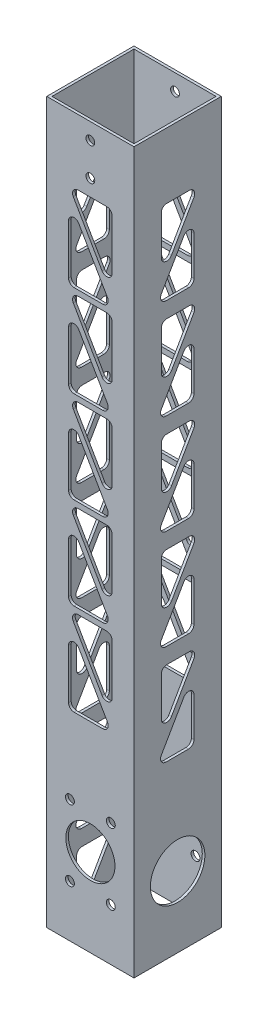
SolidWorks part; units mm, degrees
material "6061 Alloy"
ref_plane "Front Plane" through (0, 0, 0) normal (0, 0, 1) x (1, 0, 0)
ref_plane "Top Plane" through (0, 0, 0) normal (0, 1, 0) x (1, 0, 0)
ref_plane "Right Plane" through (0, 0, 0) normal (1, 0, 0) x (0, 0, -1)
sketch "Sketch1" plane through (0, 0, 0) normal (0, 1, 0) x (1, 0, 0)
  line L1 (25.4, 25.4) -> (-25.4, 25.4)
  line L2 (25.4, 25.4) -> (25.4, -25.4)
  line L3 (25.4, -25.4) -> (-25.4, -25.4)
  line L4 (-25.4, 25.4) -> (-25.4, -25.4)
  line L5 (25.4, 25.4) -> (-25.4, -25.4) construction
  line L6 (25.4, -25.4) -> (-25.4, 25.4) construction
  point P0 (0, 0)
  dimension "D1" = 50.8
extrude "Extrude-Thin1" add sketch "Sketch1" along normal blind 419.1 thin thin type one direction reverse wall 1.524
sketch "Sketch2" plane through (0, 0, 0) normal (0, 0, 1) x (1, 0, 0)
  line L0 (-36.2563, 68.2625) -> (38.5702, 68.2625) construction
  line L1 (-25.4, 0) -> (25.4, 0) construction
  line L2 (-25.4, 50.8) -> (25.4, 50.8) construction
  line L6 (25.4, 419.1) -> (25.4, 0) construction
  line L7 (-25.4, 419.1) -> (-25.4, 0) construction
  line L8 (-11.9062, 30.1778) -> (11.9063, 30.1778) construction
  line L9 (-11.9062, 71.4222) -> (11.9063, 71.4222) construction
  circle A0 centre (0, 50.8) radius 14.3002
  circle A1 centre (0, 50.8) radius 23.8125 construction
  circle A2 centre (-11.9062, 30.1778) radius 2.5908
  circle A3 centre (11.9063, 30.1778) radius 2.5908
  circle A4 centre (11.9063, 71.4222) radius 2.5908
  circle A5 centre (-11.9062, 71.4222) radius 2.5908
  point P11 (0, 50.8)
  dimension "D1" = 28.6004
  dimension "D3" = 17.4625
  dimension "D4" = 47.625
  dimension "D6" = 5.1816
  dimension "D2" = 50.8
  dimension "D5" = 60
extrude "Cut-Extrude1" cut sketch "Sketch2" along normal through all both and the other way through all
sketch "Sketch3" plane through (25.4, 0, 0) normal (1, 0, 0) x (0, 0, -1)
  line L0 (-25.4, 50.8) -> (25.4, 50.8) construction
  line L1 (-25.4, 65.1002) -> (-25.4, 36.4998) construction
  line L3 (25.4, 419.1) -> (25.4, 0) construction
  circle A0 centre (0, 41.275) radius 15.875
  point P9 (0, 50.8)
  dimension "D1" = 31.75
  dimension "D2" = 9.525
extrude "Cut-Extrude2" cut sketch "Sketch3" against normal up to surface (1.524 mm away) up to face at (23.876, 209.55, 0)
sketch "Sketch4" plane through (0, 0, 25.4) normal (0, 0, 1) x (1, 0, 0)
  line L0 (-25.4, 419.1) -> (25.4, 419.1) construction
  circle A0 centre (0, 409.575) radius 2.54
  circle A1 centre (0, 390.525) radius 2.54
  dimension "D1" = 5.08
  dimension "D2" = 9.525
  dimension "D3" = 28.575
hole_wizard "#10 Clearance Hole1" positions "Sketch5" profile "Sketch6" hole size "#10" standard "ANSI Inch" end condition through all
sketch "Sketch5" plane through (0, 0, 25.4) normal (0, 0, 1) x (1, 0, 0)
  point P0 (0, 390.525)
  point P3 (0, 409.575)
sketch "Sketch6" plane through (0, 390.525, 25.4) normal (1, 0, 0) x (0, -1, 0)
  line L0 (0, 0) -> (0, 50.8)
  line L1 (0, 50.8) -> (2.5527, 50.8)
  line L2 (2.5527, 50.8) -> (2.5527, 0)
  line L5 (2.5527, 0) -> (0, 0)
  line L11 (0, -6.35) -> (0, 107.95) construction
  dimension "Thru Hole Dia." = 5.1054
  dimension "Thru Hole Depth" = 50.8
sketch "Sketch7" plane through (0, 0, 25.4) normal (0, 0, 1) x (1, 0, 0)
  line L0 (-12.7, 419.1) -> (-12.7, 0) construction
  line L1 (12.7, 419.1) -> (12.7, 0) construction
  line L2 (-12.7, 0) -> (-25.4, 0) construction
  line L3 (-25.4, 0) -> (25.4, 0) construction
  line L4 (-25.4, 419.1) -> (-25.4, 0) construction
  line L5 (12.7, 0) -> (25.4, 0) construction
  line L6 (-25.4, 419.1) -> (25.4, 419.1) construction
  line L7 (-12.7, 381) -> (12.7, 381) construction
  line L8 (-12.7, 79.375) -> (12.7, 79.375) construction
  line L9 (-7.2007, 381) -> (9.525, 381)
  line L10 (12.7, 377.825) -> (12.7, 348.8552)
  line L11 (6.7754, 347.2677) -> (-9.9504, 376.2375)
  line L12 (-9.525, 330.6559) -> (7.2007, 330.6559)
  line L13 (-12.7, 333.8309) -> (-12.7, 362.8007)
  line L14 (-6.7754, 364.3882) -> (9.9504, 335.4184)
  line L15 (16.3954, 324.2553) -> (19.145, 325.8428) construction
  line L16 (-7.2007, 327.4809) -> (9.525, 327.4809)
  line L17 (12.7, 324.3059) -> (12.7, 295.3361)
  line L18 (6.7754, 293.7486) -> (-9.9504, 322.7184)
  line L19 (-12.7, 280.3118) -> (-12.7, 309.2816)
  line L20 (-9.525, 277.1368) -> (7.2007, 277.1368)
  line L21 (-6.7754, 310.8691) -> (9.9504, 281.8993)
  line L34 (-7.2007, 381) -> (-7.2007, 327.4809) construction
  line L35 (-7.2007, 273.9618) -> (9.525, 273.9618)
  line L36 (12.7, 270.7868) -> (12.7, 241.817)
  line L37 (6.7754, 240.2295) -> (-9.9504, 269.1993)
  line L38 (-12.7, 226.7927) -> (-12.7, 255.7626)
  line L39 (-9.525, 223.6177) -> (7.2007, 223.6177)
  line L40 (-6.7754, 257.3501) -> (9.9504, 228.3802)
  line L41 (-7.2007, 220.4427) -> (9.525, 220.4427)
  line L42 (12.7, 217.2677) -> (12.7, 188.2979)
  line L43 (6.7754, 186.7104) -> (-9.9504, 215.6802)
  line L44 (-12.7, 173.2736) -> (-12.7, 202.2435)
  line L45 (-9.525, 170.0986) -> (7.2007, 170.0986)
  line L46 (-6.7754, 203.831) -> (9.9504, 174.8611)
  line L47 (-7.2007, 166.9236) -> (9.525, 166.9236)
  line L48 (12.7, 163.7486) -> (12.7, 134.7788)
  line L49 (6.7754, 133.1913) -> (-9.9504, 162.1611)
  line L50 (-12.7, 119.7545) -> (-12.7, 148.7244)
  line L51 (-9.525, 116.5795) -> (7.2007, 116.5795)
  line L52 (-6.7754, 150.3119) -> (9.9504, 121.342)
  arc A0 (-9.9504, 376.2375) -> (-7.2007, 381) centre (-7.2007, 377.825) cw
  arc A1 (9.525, 381) -> (12.7, 377.825) centre (9.525, 377.825) cw
  arc A2 (12.7, 348.8552) -> (6.7754, 347.2677) centre (9.525, 348.8552) cw
  arc A3 (9.9504, 335.4184) -> (7.2007, 330.6559) centre (7.2007, 333.8309) cw
  arc A4 (-12.7, 362.8007) -> (-6.7754, 364.3882) centre (-9.525, 362.8007) cw
  arc A5 (-12.7, 333.8309) -> (-9.525, 330.6559) centre (-9.525, 333.8309) ccw
  arc A6 (12.7, 295.3361) -> (6.7754, 293.7486) centre (9.525, 295.3361) cw
  arc A7 (-9.9504, 322.7184) -> (-7.2007, 327.4809) centre (-7.2007, 324.3059) cw
  arc A8 (9.525, 327.4809) -> (12.7, 324.3059) centre (9.525, 324.3059) cw
  arc A9 (-12.7, 309.2816) -> (-6.7754, 310.8691) centre (-9.525, 309.2816) cw
  arc A10 (-12.7, 280.3118) -> (-9.525, 277.1368) centre (-9.525, 280.3118) ccw
  arc A11 (9.9504, 281.8993) -> (7.2007, 277.1368) centre (7.2007, 280.3118) cw
  arc A12 (12.7, 241.817) -> (6.7754, 240.2295) centre (9.525, 241.817) cw
  arc A13 (-9.9504, 269.1993) -> (-7.2007, 273.9618) centre (-7.2007, 270.7868) cw
  arc A14 (9.525, 273.9618) -> (12.7, 270.7868) centre (9.525, 270.7868) cw
  arc A15 (-12.7, 255.7626) -> (-6.7754, 257.3501) centre (-9.525, 255.7626) cw
  arc A16 (-12.7, 226.7927) -> (-9.525, 223.6177) centre (-9.525, 226.7927) ccw
  arc A17 (9.9504, 228.3802) -> (7.2007, 223.6177) centre (7.2007, 226.7927) cw
  arc A18 (12.7, 188.2979) -> (6.7754, 186.7104) centre (9.525, 188.2979) cw
  arc A19 (-9.9504, 215.6802) -> (-7.2007, 220.4427) centre (-7.2007, 217.2677) cw
  arc A20 (9.525, 220.4427) -> (12.7, 217.2677) centre (9.525, 217.2677) cw
  arc A21 (-12.7, 202.2435) -> (-6.7754, 203.831) centre (-9.525, 202.2435) cw
  arc A22 (-12.7, 173.2736) -> (-9.525, 170.0986) centre (-9.525, 173.2736) ccw
  arc A23 (9.9504, 174.8611) -> (7.2007, 170.0986) centre (7.2007, 173.2736) cw
  arc A24 (12.7, 134.7788) -> (6.7754, 133.1913) centre (9.525, 134.7788) cw
  arc A25 (-9.9504, 162.1611) -> (-7.2007, 166.9236) centre (-7.2007, 163.7486) cw
  arc A26 (9.525, 166.9236) -> (12.7, 163.7486) centre (9.525, 163.7486) cw
  arc A27 (-12.7, 148.7244) -> (-6.7754, 150.3119) centre (-9.525, 148.7244) cw
  arc A28 (-12.7, 119.7545) -> (-9.525, 116.5795) centre (-9.525, 119.7545) ccw
  arc A29 (9.9504, 121.342) -> (7.2007, 116.5795) centre (7.2007, 119.7545) cw
  point P31 (12.7, 337.0059)
  point P34 (12.7, 330.6559)
  point P37 (-12.7, 374.65)
  point P40 (-12.7, 330.6559)
  dimension "D5" = 3.175
  dimension "D1" = 12.7
  dimension "D2" = 38.1
  dimension "D3" = 79.375
  dimension "D4" = 30
  dimension "D7" = 3.175
  dimension "D8" = 3.175
  dimension "D6" = 5
extrude "Cut-Extrude3" cut sketch "Sketch7" against normal through all
sketch "Sketch8" plane through (-25.4, 0, 0) normal (-1, 0, 0) x (0, 0, 1)
  line L0 (-12.2746, 381) -> (9.525, 381) construction
  line L1 (-6.7754, 381) -> (6.35, 381)
  line L2 (9.525, 377.825) -> (9.525, 355.0912)
  line L3 (3.6004, 353.5037) -> (-9.525, 376.2375)
  line L4 (-6.35, 332.1294) -> (6.7754, 332.1294)
  line L5 (-9.525, 335.3044) -> (-9.525, 358.0382)
  line L6 (-3.6004, 359.6257) -> (9.525, 336.8919)
  line L7 (4.3689, 345.8225) -> (7.1185, 347.41) construction
  line L8 (-9.525, 419.1) -> (-9.525, 0) construction
  line L9 (-25.4, 0) -> (25.4, 0) construction
  line L10 (9.525, 0) -> (9.525, 419.1) construction
  line L11 (-25.4, 419.1) -> (25.4, 419.1) construction
  line L12 (-9.525, 392.3126) -> (-25.4, 392.3126) construction
  line L13 (-25.4, 419.1) -> (-25.4, 0) construction
  line L14 (9.525, 392.3126) -> (25.4, 392.3126) construction
  line L15 (25.4, 419.1) -> (25.4, 0) construction
  line L16 (-6.35, 273.9879) -> (6.7754, 273.9879)
  line L17 (-9.525, 277.1629) -> (-9.525, 299.8967)
  line L18 (-3.6004, 301.4842) -> (9.525, 278.7504)
  line L19 (9.525, 319.6834) -> (9.525, 296.9496)
  line L20 (3.6004, 295.3621) -> (-9.525, 318.0959)
  line L21 (-6.7754, 322.8584) -> (6.35, 322.8584)
  line L22 (-6.35, 215.8463) -> (6.7754, 215.8463)
  line L23 (-9.525, 219.0213) -> (-9.525, 241.7551)
  line L24 (-3.6004, 243.3426) -> (9.525, 220.6088)
  line L25 (9.525, 261.5419) -> (9.525, 238.8081)
  line L26 (3.6004, 237.2206) -> (-9.525, 259.9544)
  line L27 (-6.7754, 264.7169) -> (6.35, 264.7169)
  line L28 (-6.35, 157.7047) -> (6.7754, 157.7047)
  line L29 (-9.525, 160.8797) -> (-9.525, 183.6135)
  line L30 (-3.6004, 185.201) -> (9.525, 162.4672)
  line L31 (9.525, 203.4003) -> (9.525, 180.6665)
  line L32 (3.6004, 179.079) -> (-9.525, 201.8128)
  line L33 (-6.7754, 206.5753) -> (6.35, 206.5753)
  line L34 (-25.4, 87.3125) -> (25.4, 87.3125) construction
  line L35 (-6.35, 99.5632) -> (6.7754, 99.5632)
  line L36 (-9.525, 102.7382) -> (-9.525, 125.472)
  line L37 (-3.6004, 127.0595) -> (9.525, 104.3257)
  line L38 (9.525, 145.2587) -> (9.525, 122.5249)
  line L39 (3.6004, 120.9374) -> (-9.525, 143.6712)
  line L40 (-6.7754, 148.4337) -> (6.35, 148.4337)
  line L41 (-6.35, 41.4216) -> (6.7754, 41.4216)
  line L42 (-9.525, 44.5966) -> (-9.525, 67.3304)
  line L43 (-3.6004, 68.9179) -> (9.525, 46.1841)
  line L44 (9.525, 87.1172) -> (9.525, 64.3834)
  line L45 (3.6004, 62.7959) -> (-9.525, 85.5297)
  line L46 (-6.7754, 90.2922) -> (6.35, 90.2922)
  line L50 (9.525, 28.9756) -> (9.525, 6.2418)
  line L51 (3.6004, 4.6543) -> (-9.525, 27.3881)
  line L52 (-6.7754, 32.1506) -> (6.35, 32.1506)
  line L53 (-6.35, -16.7199) -> (6.7754, -16.7199) [skipped]
  line L54 (-3.6004, 10.7764) -> (9.525, -11.9574) [skipped]
  line L55 (-9.525, -13.5449) -> (-9.525, 9.1889) [skipped]
  arc A0 (-9.525, 376.2375) -> (-6.7754, 381) centre (-6.7754, 377.825) cw
  arc A1 (6.35, 381) -> (9.525, 377.825) centre (6.35, 377.825) cw
  arc A2 (9.525, 355.0912) -> (3.6004, 353.5037) centre (6.35, 355.0912) cw
  arc A3 (9.525, 336.8919) -> (6.7754, 332.1294) centre (6.7754, 335.3044) cw
  arc A4 (-9.525, 358.0382) -> (-3.6004, 359.6257) centre (-6.35, 358.0382) cw
  arc A5 (-9.525, 335.3044) -> (-6.35, 332.1294) centre (-6.35, 335.3044) ccw
  arc A6 (-9.525, 277.1629) -> (-6.35, 273.9879) centre (-6.35, 277.1629) ccw
  arc A7 (-9.525, 299.8967) -> (-3.6004, 301.4842) centre (-6.35, 299.8967) cw
  arc A8 (9.525, 278.7504) -> (6.7754, 273.9879) centre (6.7754, 277.1629) cw
  arc A9 (9.525, 296.9496) -> (3.6004, 295.3621) centre (6.35, 296.9496) cw
  arc A10 (6.35, 322.8584) -> (9.525, 319.6834) centre (6.35, 319.6834) cw
  arc A11 (-9.525, 318.0959) -> (-6.7754, 322.8584) centre (-6.7754, 319.6834) cw
  arc A12 (-9.525, 219.0213) -> (-6.35, 215.8463) centre (-6.35, 219.0213) ccw
  arc A13 (-9.525, 241.7551) -> (-3.6004, 243.3426) centre (-6.35, 241.7551) cw
  arc A14 (9.525, 220.6088) -> (6.7754, 215.8463) centre (6.7754, 219.0213) cw
  arc A15 (9.525, 238.8081) -> (3.6004, 237.2206) centre (6.35, 238.8081) cw
  arc A16 (6.35, 264.7169) -> (9.525, 261.5419) centre (6.35, 261.5419) cw
  arc A17 (-9.525, 259.9544) -> (-6.7754, 264.7169) centre (-6.7754, 261.5419) cw
  arc A18 (-9.525, 160.8797) -> (-6.35, 157.7047) centre (-6.35, 160.8797) ccw
  arc A19 (-9.525, 183.6135) -> (-3.6004, 185.201) centre (-6.35, 183.6135) cw
  arc A20 (9.525, 162.4672) -> (6.7754, 157.7047) centre (6.7754, 160.8797) cw
  arc A21 (9.525, 180.6665) -> (3.6004, 179.079) centre (6.35, 180.6665) cw
  arc A22 (6.35, 206.5753) -> (9.525, 203.4003) centre (6.35, 203.4003) cw
  arc A23 (-9.525, 201.8128) -> (-6.7754, 206.5753) centre (-6.7754, 203.4003) cw
  arc A24 (-9.525, 102.7382) -> (-6.35, 99.5632) centre (-6.35, 102.7382) ccw
  arc A25 (-9.525, 125.472) -> (-3.6004, 127.0595) centre (-6.35, 125.472) cw
  arc A26 (9.525, 104.3257) -> (6.7754, 99.5632) centre (6.7754, 102.7382) cw
  arc A27 (9.525, 122.5249) -> (3.6004, 120.9374) centre (6.35, 122.5249) cw
  arc A28 (6.35, 148.4337) -> (9.525, 145.2587) centre (6.35, 145.2587) cw
  arc A29 (-9.525, 143.6712) -> (-6.7754, 148.4337) centre (-6.7754, 145.2587) cw
  arc A30 (-9.525, 44.5966) -> (-6.35, 41.4216) centre (-6.35, 44.5966) ccw
  arc A31 (-9.525, 67.3304) -> (-3.6004, 68.9179) centre (-6.35, 67.3304) cw
  arc A32 (9.525, 46.1841) -> (6.7754, 41.4216) centre (6.7754, 44.5966) cw
  arc A33 (9.525, 64.3834) -> (3.6004, 62.7959) centre (6.35, 64.3834) cw
  arc A34 (6.35, 90.2922) -> (9.525, 87.1172) centre (6.35, 87.1172) cw
  arc A35 (-9.525, 85.5297) -> (-6.7754, 90.2922) centre (-6.7754, 87.1172) cw
  arc A39 (9.525, 6.2418) -> (3.6004, 4.6543) centre (6.35, 6.2418) cw
  arc A40 (6.35, 32.1506) -> (9.525, 28.9756) centre (6.35, 28.9756) cw
  arc A41 (-9.525, 27.3881) -> (-6.7754, 32.1506) centre (-6.7754, 28.9756) cw
  arc A42 (9.525, -11.9574) -> (6.7754, -16.7199) centre (6.7754, -13.5449) cw [skipped]
  arc A43 (-9.525, 9.1889) -> (-3.6004, 10.7764) centre (-6.35, 9.1889) cw [skipped]
  arc A44 (-9.525, -13.5449) -> (-6.35, -16.7199) centre (-6.35, -13.5449) ccw [skipped]
  point P150 (7.1718, 3.175)
  dimension "D2" = 3.175
  dimension "D1" = 30
  dimension "D3" = 38.1
  dimension "D4" = 15.875
  dimension "D5" = 3.175
  dimension "D7" = 3.175
  dimension "D8" = 87.3125
  dimension "D6" = 7
extrude "Cut-Extrude4" cut sketch "Sketch8" against normal through all contours A14 L24 A13 L23 A12 L22 | A17 L26 A15 L25 A16 L27 | A8 L18 A7 L17 A6 L16 | A11 L20 A9 L19 A10 L21 | L5 A5 L4 A3 L6 A4 | A2 L2 A1 L1 A0 L3 | A23 L32 A21 L31 A22 L33 | A20 L30 A19 L29 A18 L28 | A29 L39 A27 L38 A28 L40 | A26 L37 A25 L36 A24 L35 region at (-25.4, 369.365, 2.0868) region at (-25.4, 343.7645, -2.0868) region at (-25.4, 285.6229, -2.0868) region at (-25.4, 311.2234, 2.0868) region at (-25.4, 227.4813, -2.0868) region at (-25.4, 253.0819, 2.0868) region at (-25.4, 169.3398, -2.0868) region at (-25.4, 194.9403, 2.0868) region at (-25.4, 111.1982, -2.0868) region at (-25.4, 136.7987, 2.0868)
extrude "Cut-Extrude5" cut sketch "Sketch8<4>" against normal up to next contours A41 L51 A39 L50 A40 L52 | A32 L43 A31 L42 A30 L41 | A35 L45 A33 L44 A34 L46 region at (-25.4, 53.0566, -2.0868) region at (-25.4, 78.6572, 2.0868) region at (-25.4, 20.5156, 2.0868)
sketch "Sketch8<4>" plane through (-25.4, 0, 0) normal (-1, 0, 0) x (0, 0, 1) same geometry as "Sketch8"
